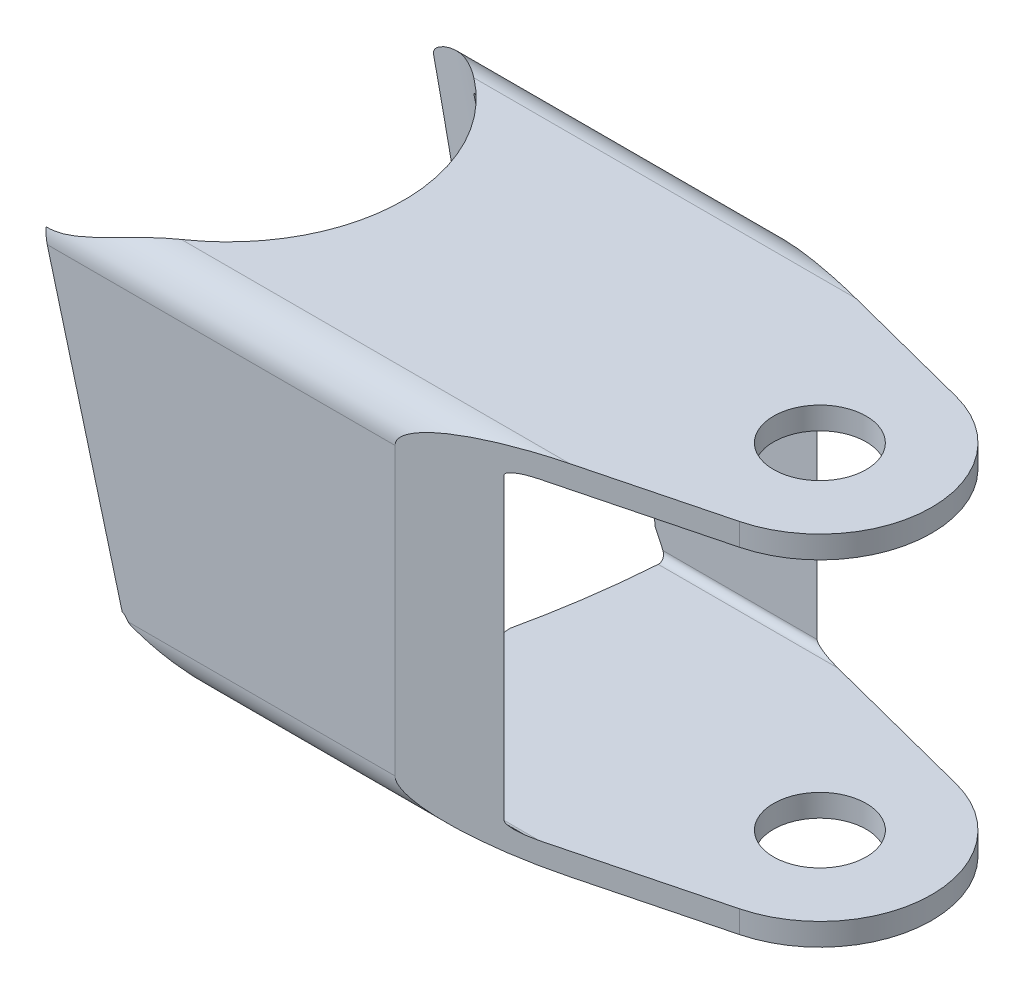
SolidWorks part; units mm, degrees
ref_plane "Front Plane" through (0, 0, 0) normal (0, 0, 1) x (1, 0, 0)
ref_plane "Top Plane" through (0, 0, 0) normal (0, 1, 0) x (1, 0, 0)
ref_plane "Right Plane" through (0, 0, 0) normal (1, 0, 0) x (0, 0, -1)
sketch "Sketch1" plane through (0, 0, 0) normal (1, 0, 0) x (0, 0, -1)
  line L1 (-10.16, 12.7) -> (10.16, 12.7)
  line L2 (-12.7, 10.16) -> (-12.7, -10.16)
  line L3 (-10.16, -12.7) -> (10.16, -12.7)
  line L4 (12.7, 10.16) -> (12.7, -10.16)
  arc A0 (-10.16, 12.7) -> (-12.7, 10.16) centre (-10.16, 10.16) ccw
  arc A1 (-10.16, -12.7) -> (-12.7, -10.16) centre (-10.16, -10.16) cw
  arc A2 (10.16, 12.7) -> (12.7, 10.16) centre (10.16, 10.16) cw
  arc A3 (12.7, -10.16) -> (10.16, -12.7) centre (10.16, -10.16) cw
  point P4 (0, -12.7)
  point P7 (0, 0)
  point P15 (12.7, 0)
  dimension "D3" = 2.54
  dimension "D4" = 2.54
  dimension "D5" = 2.54
  dimension "D6" = 2.54
  dimension "D1" = 25.4
  dimension "D2" = 20.32
extrude "Boss-Extrude1" add sketch "Sketch1" along normal blind 25.4 and the other way blind 34.925
sketch "Sketch11" plane through (25.4, 0, 0) normal (1, 0, 0) x (0, 0, -1)
  line L0 (-10.16, -12.7) -> (10.16, -12.7) construction
  line L1 (-10.6045, 11.1125) -> (10.6045, 11.1125)
  line L2 (-11.1125, 10.6045) -> (-11.1125, -10.6045)
  line L3 (-10.6045, -11.1125) -> (10.6045, -11.1125)
  line L4 (11.1125, 10.6045) -> (11.1125, -10.6045)
  line L5 (10.16, 12.7) -> (-10.16, 12.7) construction
  line L6 (12.7, -10.16) -> (12.7, 10.16) construction
  line L7 (-12.7, 10.16) -> (-12.7, -10.16) construction
  arc A0 (10.6045, 11.1125) -> (11.1125, 10.6045) centre (10.6045, 10.6045) cw
  arc A1 (10.6045, -11.1125) -> (11.1125, -10.6045) centre (10.6045, -10.6045) ccw
  arc A2 (-11.1125, -10.6045) -> (-10.6045, -11.1125) centre (-10.6045, -10.6045) ccw
  arc A3 (-10.6045, 11.1125) -> (-11.1125, 10.6045) centre (-10.6045, 10.6045) ccw
  dimension "D1" = 1.5875
  dimension "D2" = 1.5875
  dimension "D3" = 1.5875
  dimension "D4" = 1.5875
  dimension "D5" = 0.508
extrude "Cut-Extrude4" cut sketch "Sketch11" against normal through all
sketch "Sketch12" plane through (0, 12.7, 0) normal (0, 1, 0) x (1, 0, 0)
  line L1 (0, 12.7) -> (50.8, 12.7)
  line L2 (50.8, 12.7) -> (50.8, -12.7)
  line L12 (50.8, -12.7) -> (0, -12.7)
  line L13 (19.4444, -7.6861) -> (0, -12.7)
  line L14 (19.4444, 7.6861) -> (0, 12.7)
  line L15 (-34.925, -12.7) -> (25.4, -12.7) construction
  line L16 (-34.925, 12.7) -> (25.4, 12.7) construction
  line L18 (25.4, 10.16) -> (25.4, -10.16) construction
  arc A1 (19.4444, -7.6861) -> (19.4444, 7.6861) centre (17.4625, 0) ccw
  point P8 (18.1688, 9.2165)
  line M6 (-34.925, -10.16) -> (25.4, -10.16)
  line M7 (25.4, -10.16) -> (25.4, 10.16)
  line M8 (25.4, 10.16) -> (-34.925, 10.16)
  line M9 (-34.925, 10.16) -> (-34.925, -10.16)
  dimension "D2" = 50.8
  dimension "D1" = 17.4625
extrude "Cut-Extrude5" cut sketch "Sketch12" against normal through all contours M9 M8 M7 M6 | M7 M8 M9 | M6 M7 region at (34.888, 12.7, 0) region at (20.955, 12.7, -8.1283) region at (20.955, 12.7, 8.1283)
sketch "Sketch14" plane through (0, 12.7, 0) normal (0, 1, 0) x (1, 0, 0)
  circle A0 centre (17.4625, 0) radius 3.2893
  arc A2 (19.4444, -7.6861) -> (19.4444, 7.6861) centre (17.4625, 0) ccw construction
  point P0 (17.4625, 0)
  point P6 (25.4, 0)
  dimension "D2" = 6.5786
  dimension "D1" = 7.9375
  dimension "D3" = 17.4625
extrude "Cut-Extrude6" cut sketch "Sketch14" against normal through all
ref_axis "Axis1" through (-4.8069, -64.2656, 0.4237) along (-0.2581, 0.9661, -0.0075)
ref_axis "Axis2" through (-54.9148, -19.3332, 0) along (0.9661, 0.2581, 0)
ref_axis "Axis3" through (-41.6758, -16.0158, -28.1321) along (0.6127, 0.1697, 0.7719)
ref_axis "Axis4" through (-15.6695, -9.112, -33.6479) along (-0.1086, -0.0213, 0.9939)
ref_axis "Axis5" through (5.1797, -58.7099, -99.3389) along (-0.2163, 0.431, 0.876)
ref_point "Point1"
ref_point "Point2"
ref_point "Point3"
ref_point "Point4"
ref_point "Point5"
ref_plane "Plane1" through (-18.5809, -12.7, 0.0223) normal (-0.2581, 0.9661, -0.0075) x (0.9661, 0.2581, -0.002)
ref_plane "Plane2" through (-34.925, -13.9936, 0) normal (0.9661, 0.2581, 0) x (0, 0, -1)
ref_plane "Plane3" through (-29.4271, -12.6238, -12.7) normal (0.6127, 0.1697, 0.7719) x (0.7903, -0.1315, -0.5984)
ref_plane "Plane4" through (-17.9589, -9.5605, -12.7) normal (-0.1086, -0.0213, 0.9939) x (0.9941, -0.0023, 0.1086)
ref_plane "Plane5" through (-16.2113, -16.0812, -12.7) normal (-0.2163, 0.431, 0.876) x (0.9763, 0.0955, 0.1941)
sketch "Sketch15" plane through (-18.5809, -12.7, 0.0223) normal (-0.2581, 0.9661, -0.0075) x (0.9661, 0.2581, -0.002)
  circle A0 centre (0, 0) radius 12.7
  dimension "D1" = 25.4
sketch "Sketch16" plane through (-34.925, -13.9936, 0) normal (0.9661, 0.2581, 0) x (0, 0, -1)
  circle A0 centre (0, 0) radius 12.7
  dimension "D1" = 25.4
sketch "Sketch17" plane through (-29.4271, -12.6238, -12.7) normal (0.6127, 0.1697, 0.7719) x (0.7903, -0.1315, -0.5984)
  circle A0 centre (0, 0) radius 12.7
  dimension "D1" = 25.4
sketch "Sketch18" plane through (-17.9589, -9.5605, -12.7) normal (-0.1086, -0.0213, 0.9939) x (0.9941, -0.0023, 0.1086)
  circle A0 centre (0, 0) radius 12.7
  dimension "D1" = 25.4
sketch "Sketch19" plane through (-16.2113, -16.0812, -12.7) normal (-0.2163, 0.431, 0.876) x (0.9763, 0.0955, 0.1941)
  circle A0 centre (0, 0) radius 12.7
  dimension "D1" = 25.4
extrude "Cut-Extrude7" cut sketch "Sketch15" against normal blind 25.4 and the other way blind 38.1
extrude "Cut-Extrude21" cut sketch "Sketch16" against normal blind 25.4 and the other way blind 14.732
extrude "Cut-Extrude22" cut sketch "Sketch17" against normal blind 12.7 and the other way blind 16.51
extrude "Cut-Extrude23" cut sketch "Sketch18" against normal blind 12.7 and the other way blind 16.51
extrude "Cut-Extrude24" cut sketch "Sketch19" against normal blind 12.7 and the other way blind 12.7
ref_axis "Axis6" through (-30.7246, 32.7621, -0.3315) along (0.2581, -0.9661, 0.0075)
ref_plane "Plane6" through (-20.5099, -5.4785, 0) normal (0.9661, 0.2581, 0) x (0.2581, -0.9661, 0.0075)
ref_point "Point7"
sketch "Sketch20" plane through (-20.5099, -5.4785, 0) normal (0.9661, 0.2581, 0) x (0.2581, -0.9661, 0.0075)
  line L1 (-29.2065, -20.4458) -> (29.2065, -20.4458)
  line L2 (-29.2065, -20.4458) -> (-29.2065, 20.4458)
  line L3 (-29.2065, 20.4458) -> (29.2065, 20.4458)
  line L4 (29.2065, -20.4458) -> (29.2065, 20.4458)
  line L5 (-29.2065, -20.4458) -> (29.2065, 20.4458) construction
  line L6 (-29.2065, 20.4458) -> (29.2065, -20.4458) construction
  point P0 (0, 0)
extrude "Cut-Extrude25" cut sketch "Sketch20" against normal through all
